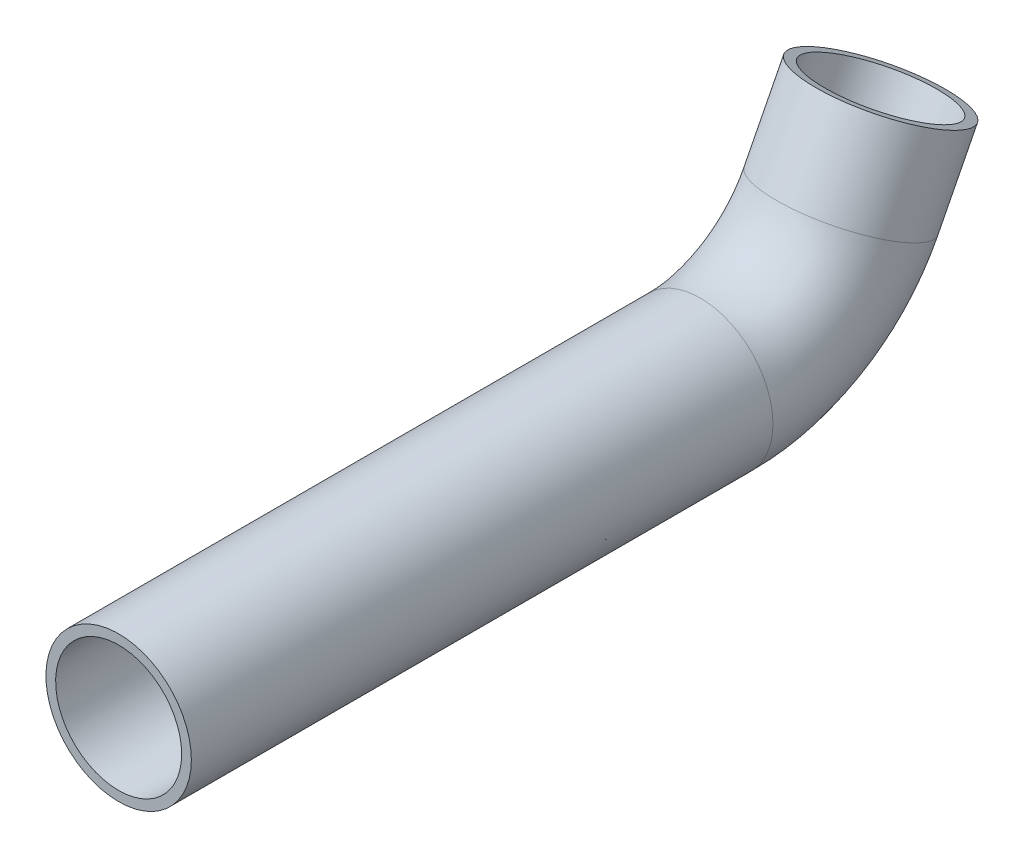
SolidWorks part; units mm, degrees
ref_plane "Front Plane" through (0, 0, 0) normal (0, 0, 1) x (1, 0, 0)
ref_plane "Top Plane" through (0, 0, 0) normal (0, 1, 0) x (1, 0, 0)
ref_plane "Right Plane" through (0, 0, 0) normal (1, 0, 0) x (0, 0, -1)
sketch "Sketch1" plane through (0, 0, 0) normal (0, 0, 1) x (1, 0, 0)
  circle A0 centre (0, 0) radius 1905
extrude "Boss-Extrude1" add sketch "Sketch1" along normal blind 15138.4
shell "Shell1" thickness 254 removed face at (1905, 0, 0) removed face at (1905, 0, 15138.4)
sketch "Sketch2" plane through (0, 0, 0) normal (0, 0, -1) x (-1, 0, 0)
  circle A0 centre (0, 0) radius 1905
sketch "Sketch3" plane through (0, 0, 0) normal (1, 0, 0) x (0, 0, -1)
  line L0 (0, 0) -> (101.6, 0)
  arc A0 (101.6, 0) -> (3790.5452, 2260.5885) centre (101.6, 4140.2) ccw
sweep "Sweep1" add profiles "Sketch2" path "Sketch3"
sketch "Sketch4" plane through (0, 3327.9723, -1695.6866) normal (0, 0.891, -0.454) x (1, 0, 0)
  circle A0 centre (0, 2351.1148) radius 1905
extrude "Boss-Extrude2" add sketch "Sketch4" along normal blind 2286
shell "Shell2" thickness 254 removed face at (0, 5162.2813, -3131.0001) removed face at (1651, 0, 0)
